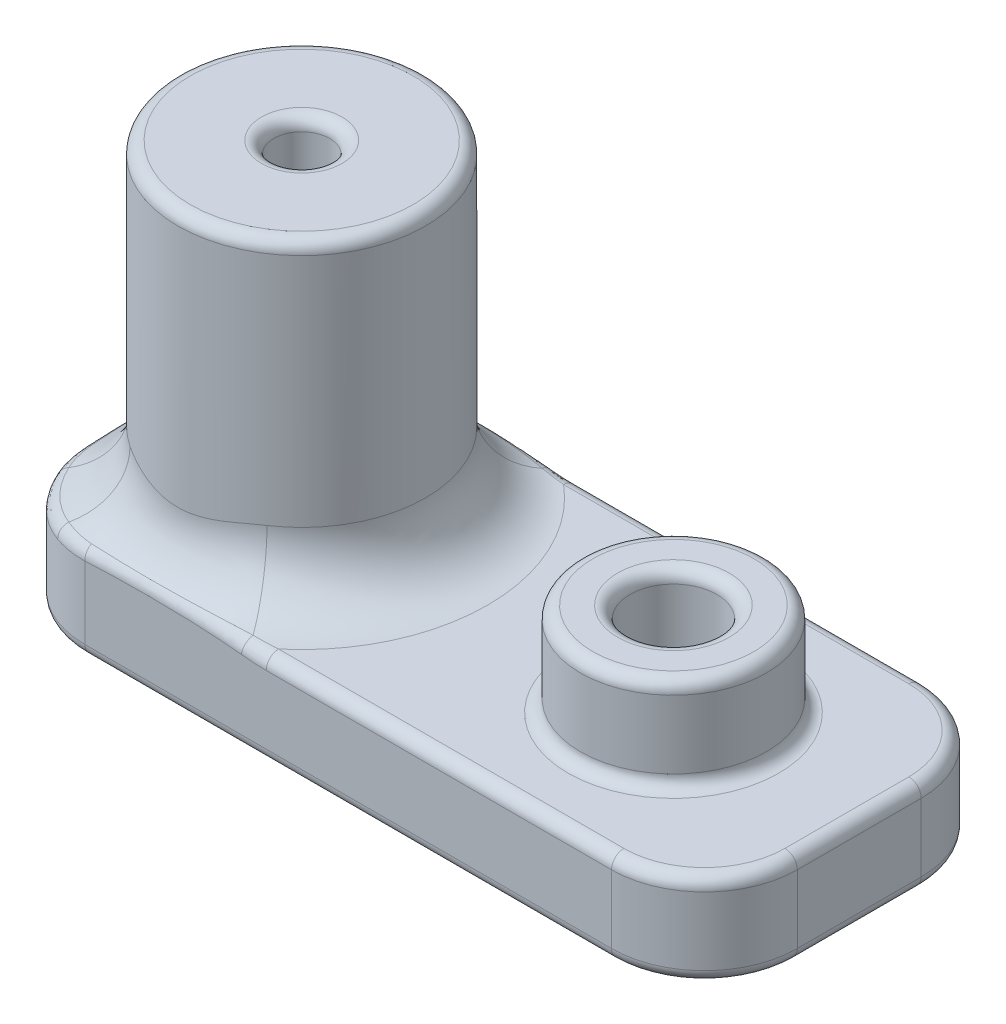
SolidWorks part; units mm, degrees
ref_plane "Front Plane" through (0, 0, 0) normal (0, 0, 1) x (1, 0, 0)
ref_plane "Top Plane" through (0, 0, 0) normal (0, 1, 0) x (1, 0, 0)
ref_plane "Right Plane" through (0, 0, 0) normal (1, 0, 0) x (0, 0, -1)
sketch "Sketch1" plane through (0, 0, 0) normal (0, 1, 0) x (1, 0, 0)
  line L1 (0, 0) -> (23, 0)
  line L2 (0, 0) -> (0, -10)
  line L3 (0, -10) -> (23, -10)
  line L4 (23, 0) -> (23, -10)
  dimension "D1" = 10
  dimension "D2" = 23
extrude "Boss-Extrude1" add sketch "Sketch1" along normal blind 3
sketch "Sketch2" plane through (0, 3, 0) normal (0, 1, 0) x (1, 0, 0)
  line L0 (23, 0) -> (0, 0) construction
  line L1 (0, 0) -> (0, -10) construction
  circle A0 centre (5, -5) radius 4
  dimension "D1" = 8
  dimension "D2" = 5
  dimension "D3" = 5
extrude "Boss-Extrude2" add sketch "Sketch2" along normal blind 10
sketch "Sketch3" plane through (0, 13, 0) normal (0, 1, 0) x (1, 0, 0)
  circle A0 centre (5, -5) radius 0.9
  dimension "D1" = 1.8
extrude "Cut-Extrude1" cut sketch "Sketch3" against normal through all
sketch "Sketch4" plane through (0, 3, 0) normal (0, 1, 0) x (1, 0, 0)
  line L5 (23, -10) -> (23, 0) construction
  circle A0 centre (17, -5) radius 1.4
  circle A1 centre (5, -5) radius 4 construction
  point P4 (23, -5)
  dimension "D1" = 0
  dimension "D3" = 2.8
  dimension "D2" = 12
extrude "Cut-Extrude2" cut sketch "Sketch4" against normal through all
sketch "Sketch6" plane through (0, 3, 0) normal (0, 1, 0) x (1, 0, 0)
  circle A0 centre (17, -5) radius 1.4
  circle A1 centre (17, -5) radius 3
  dimension "D1" = 6
  dimension "D2" = 2.8
extrude "Boss-Extrude3" add sketch "Sketch6" along normal blind 3
fillet "Fillet1" radius 2 1 edges at (5, 3, 9)
fillet "Fillet3" radius 3 4 edges at (23, 1.5, 10) (23, 1.5, 0) (0, 1.5, 10) (0, 1.5, 0)
fillet "Fillet4" radius 0.4 20 edges at (5.6583, 3, 10) (2.8279, 3.0015, 9.9951) (2, 3.0218, 0.1716) (5.6583, 3, 0) (22.1213, 0, 0.8787) (11.5, 0, 0) (0.8787, 0, 0.8787) (0, 0, 5) (0.8787, 0, 9.1213) (11.5, 0, 10) (22.1213, 0, 9.1213) (23, 0, 5) (5, 0, 5.9) (14.1583, 3, 0) (22.1213, 3, 0.8787) (23, 3, 5) (22.1213, 3, 9.1213) (14.1583, 3, 10) (17, 0, 6.4) (17, 3, 8)
fillet "Fillet5" radius 0.4 4 edges at (5, 13, 9) (5, 13, 5.9) (17, 6, 6.4) (17, 6, 8)
